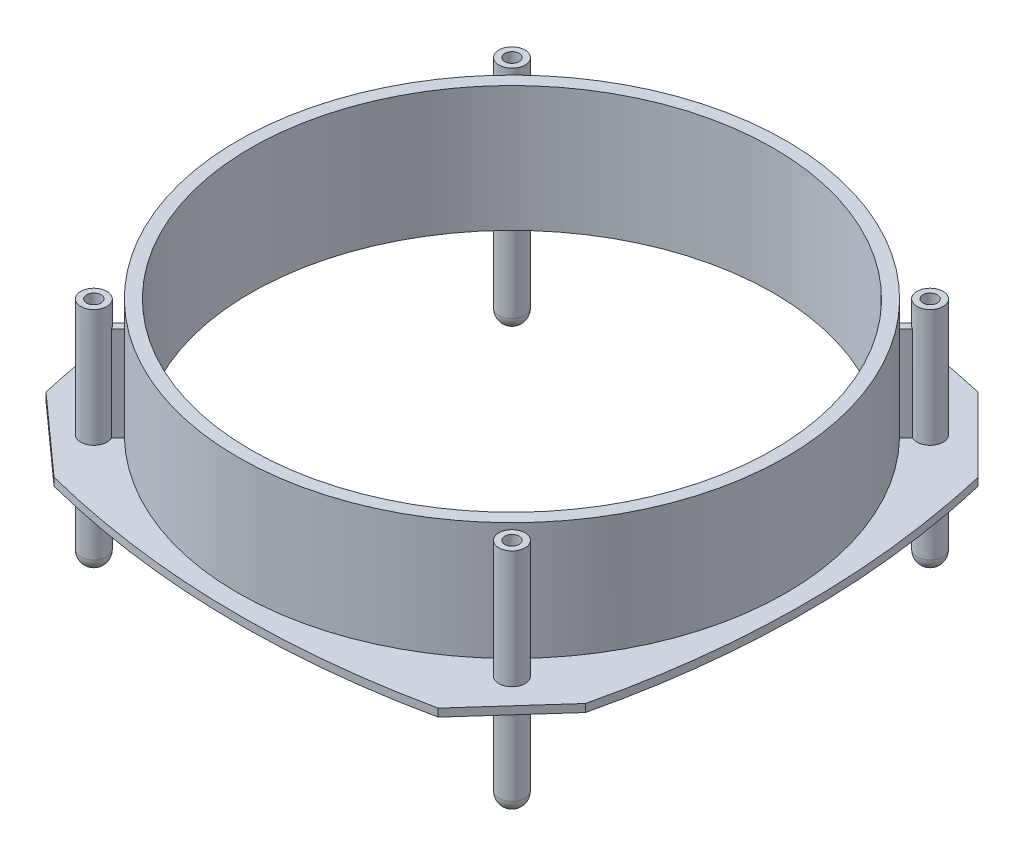
SolidWorks part; units mm, degrees
ref_plane "Front Plane" through (0, 0, 0) normal (0, 0, 1) x (1, 0, 0)
ref_plane "Top Plane" through (0, 0, 0) normal (0, 1, 0) x (1, 0, 0)
ref_plane "Right Plane" through (0, 0, 0) normal (1, 0, 0) x (0, 0, -1)
sketch "Sketch2" plane through (0, 0, 0) normal (0, 1, 0) x (1, 0, 0)
  line L0 (3824.4294, -5236.7276) -> (5157.6927, -3749.6242)
  line L2 (5163.9685, 3752.3444) -> (3751.2089, 5164.1439)
  line L4 (-3751.7702, 5163.5828) -> (-5163.7079, 3750.9614)
  line L6 (-5163.0762, -3751.9198) -> (-3675.9728, -5085.183)
  circle A0 centre (0, 0) radius 5000
  spline S0 degree 2 poles (-3751.7702, 5163.5828) (-0.3376, 6037.3855) (3751.2089, 5164.1439) knots 0 0 0 1 1 1
  spline S1 degree 2 poles (-5163.7079, 3750.9614) (-6037.5496, -0.539) (-5163.0762, -3751.9198) knots 0 0 0 1 1 1
  spline S2 degree 2 poles (-3675.9728, -5085.183) (54.6713, -6041.0227) (3824.4294, -5236.7276) knots 0 0 0 1 1 1
  spline S3 degree 2 poles (5163.9685, 3752.3444) (6040.8667, 0.5969) (5157.6927, -3749.6242) knots 0 0 0 1 1 1
extrude "Boss-Extrude2" add sketch "Sketch2" along normal blind 150
sketch "Sketch3" plane through (0, 0, 0) normal (0, 1, 0) x (1, 0, 0)
  circle A0 centre (0, 0) radius 5244.2465
extrude "Boss-Extrude3" add sketch "Sketch3" along normal blind 2400
sketch "Sketch4" plane through (0, 2400, 0) normal (0, 1, 0) x (1, 0, 0)
  circle A0 centre (0, 0) radius 5000
extrude "Cut-Extrude1" cut sketch "Sketch4" against normal blind 3000 contours A0
sketch "Sketch5" plane through (0, 150, 0) normal (0, 1, 0) x (1, 0, 0)
  circle A0 centre (-4000, -4000) radius 250
  circle A1 centre (4000, -4000) radius 250
  circle A2 centre (4000, 4000) radius 250
sketch "Sketch7" plane through (0, 0, 0) normal (0, -1, 0) x (-1, 0, 0)
  circle A0 centre (4000, 4000) radius 250
sketch "Sketch8" plane through (0, 150, 0) normal (0, 1, 0) x (1, 0, 0)
  line L0 (3785.2923, -3871.9351) -> (3569.5398, -3651.2442)
  circle A0 centre (4000, -4000) radius 250 construction
  point P0 (3786.5537, -3873.2254)
  point P4 (3786.5537, -3873.2254)
  point P5 (3786.5537, -3873.2254)
  point P6 (3888.8138, -3773.2537)
  point P11 (3890.7516, -3775.1339)
extrude "Extrude-Thin9" [suppressed] add sketch "Sketch8" along normal blind 2400 thin thin type one direction wall 128
extrude "Boss-Extrude11" [suppressed] add sketch "Sketch5" along normal blind 2850 and the other way blind 1900 contours A1
sketch "Sketch9" plane through (0, 0, 0) normal (0, -1, 0) x (-1, 0, 0)
  circle A0 centre (4000, 4000) radius 250
extrude "Boss-Extrude12" add sketch "Sketch7" against normal blind 2400 contours A0
extrude "Boss-Extrude13" add sketch "Sketch9" along normal blind 2000 contours A0
fillet "Fillet1" radius 250 2 edges at (-4000, 0, -4250) (-4000, -2000, -4250)
sketch "Sketch10" plane through (0, 2400, 0) normal (0, 1, 0) x (1, 0, 0)
  circle A0 centre (-4000, 4000) radius 137.4456
extrude "Cut-Extrude2" cut sketch "Sketch10" against normal blind 500
sketch "Sketch13" plane through (0, 150, 0) normal (0, 1, 0) x (1, 0, 0)
  line L0 (-3779.8016, 3881.6249) -> (-3656.9811, 3758.8045)
  line L1 (-3758.8045, 3656.9811) -> (-3881.6249, 3779.8016)
  circle A0 centre (-4000, 4000) radius 250 construction
  circle A1 centre (0, 0) radius 5244.2465 construction
  dimension "D1" = 144
extrude "Extrude-Thin10" add sketch "Sketch13" along normal blind 1800 thin thin type one direction wall 72
ref_axis "Axis1" through (0, 3250, 0) along (0, -1, 0)
pattern_circular "CirPattern1" count 4 over 360 about axis through (0, 3250, 0) along (0, -1, 0) of "Boss-Extrude12", "Boss-Extrude13", "Fillet1", "Cut-Extrude2", "Extrude-Thin10"
